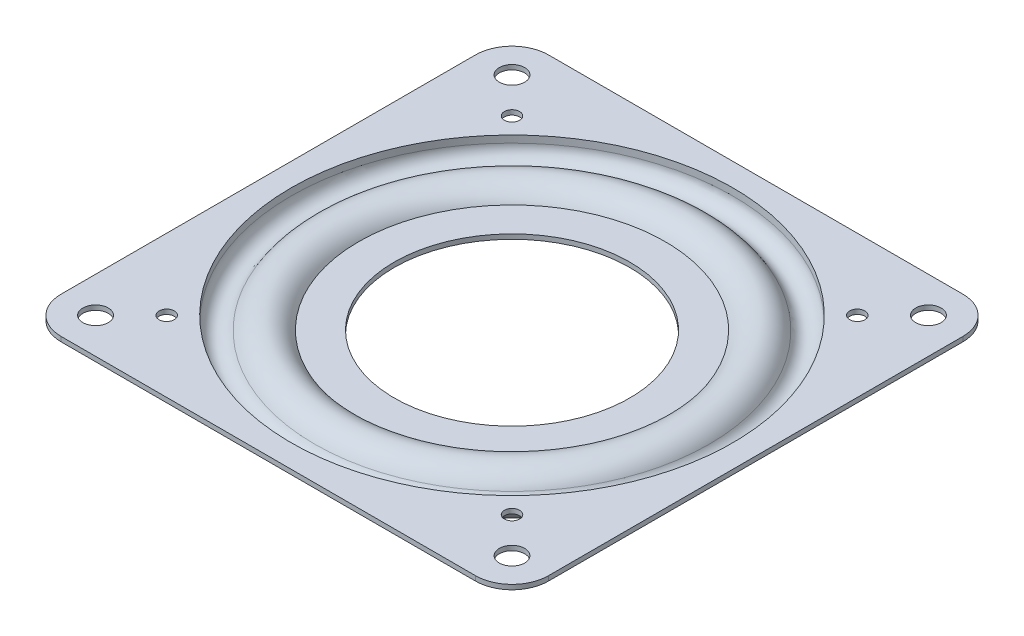
SolidWorks part; units mm, degrees
material "Plain Carbon Steel"
ref_plane "Front Plane" through (0, 0, 0) normal (0, 0, 1) x (1, 0, 0)
ref_plane "Top Plane" through (0, 0, 0) normal (0, 1, 0) x (1, 0, 0)
ref_plane "Right Plane" through (0, 0, 0) normal (1, 0, 0) x (0, 0, -1)
sketch "Sketch1" plane through (0, 0, 0) normal (0, 1, 0) x (1, 0, 0)
  line L0 (0, -53.8815) -> (-53.8815, 0) construction
  line L1 (-38.1, 38.1) -> (38.1, 38.1) construction
  line L2 (-38.1, 38.1) -> (-38.1, -38.1) construction
  line L3 (-38.1, -38.1) -> (38.1, -38.1) construction
  line L4 (38.1, 38.1) -> (38.1, -38.1) construction
  line L5 (0, -38.1) -> (0, 38.1) construction
  line L6 (-38.1, 0) -> (38.1, 0) construction
  line L7 (0, -53.8815) -> (53.8815, 0) construction
  line L8 (-53.8815, 0) -> (0, 53.8815) construction
  line L9 (53.8815, 0) -> (0, 53.8815) construction
  line L10 (0, -53.8815) -> (0, 53.8815) construction
  line L11 (-53.8815, 0) -> (53.8815, 0) construction
  line L12 (38.1, -38.1) -> (-38.1, 38.1) construction
  line L13 (38.1, 38.1) -> (-38.1, -38.1) construction
  line L15 (-26.9875, 26.9875) -> (26.9875, 26.9875) construction
  line L16 (-26.9875, 26.9875) -> (-26.9875, -26.9875) construction
  line L17 (-26.9875, -26.9875) -> (26.9875, -26.9875) construction
  line L18 (26.9875, 26.9875) -> (26.9875, -26.9875) construction
  line L19 (-32.5437, 32.5437) -> (32.5437, 32.5437) construction
  line L20 (-32.5437, 32.5437) -> (-32.5437, -32.5437) construction
  line L21 (-32.5437, -32.5437) -> (32.5437, -32.5437) construction
  line L22 (32.5437, 32.5437) -> (32.5437, -32.5437) construction
  circle A0 centre (0, 0) radius 16.637 construction
  circle A1 centre (32.5437, -32.5437) radius 1.9844 construction
  circle A2 centre (-32.5437, -32.5437) radius 1.9844 construction
  circle A3 centre (-32.5437, 32.5437) radius 1.9844 construction
  circle A4 centre (32.5437, 32.5437) radius 1.9844 construction
  circle A5 centre (26.9875, 26.9875) radius 1.1906 construction
  circle A6 centre (-26.9875, 26.9875) radius 1.1906 construction
  circle A7 centre (-26.9875, -26.9875) radius 1.1906 construction
  circle A8 centre (26.9875, -26.9875) radius 1.1906 construction
  dimension "ID" = 33.274
  dimension "Inner Mounting Hole Dia." = 2.3813
  dimension "Outer Mounting Hole Dia." = 3.9688
  dimension "Length" = 76.2
  dimension "Width" = 76.2
  dimension "Inner Mounting Length" = 53.975
  dimension "Outer Mounting Length" = 65.0875
sketch "Sketch2" plane through (0, 0, 0) normal (0, 0, 1) x (1, 0, 0)
  line L0 (0, 3.937) -> (0, -3.937) construction
  line L1 (-38.1, 3.937) -> (38.1, 3.937) construction
  line L2 (-38.1, 3.937) -> (-38.1, -3.937) construction
  line L3 (-38.1, -3.937) -> (38.1, -3.937) construction
  line L4 (38.1, 3.937) -> (38.1, -3.937) construction
  line L5 (-38.1, 0) -> (38.1, 0) construction
  line L6 (-38.1, 3.2004) -> (38.1, 3.2004) construction
  line L7 (-38.1, -3.2004) -> (38.1, -3.2004) construction
  point P8 (0, 0)
  dimension "Overall Height" = 7.874
  dimension "Plate Thickness" = 0.7366
sketch "Sketch3" plane through (0, 0, 0) normal (0, 0, 1) x (1, 0, 0)
  line L0 (38.1, 3.937) -> (34.5177, 3.937)
  line L1 (-38.1, 3.937) -> (38.1, 3.937) construction
  line L2 (34.5177, 3.937) -> (34.5177, 2.8346)
  line L3 (23.943, 1.9406) -> (18.4086, 1.9406)
  line L4 (38.1, -3.937) -> (34.5177, -3.937)
  line L5 (-38.1, -3.937) -> (38.1, -3.937) construction
  line L6 (34.5177, -3.937) -> (34.5177, -2.8346)
  line L7 (34.5177, -2.8346) -> (34.5177, 2.8346) construction
  line L8 (23.528, -0.8661) -> (18.4086, -0.8661)
  line L9 (18.4086, 2.6772) -> (20.9683, 2.6772)
  line L10 (23.528, -0.8661) -> (34.5177, -0.8661) construction
  line L11 (16.637, 3.937) -> (16.637, -3.937) construction
  line L12 (16.637, 0) -> (-16.637, 0) construction
  line L13 (18.4086, 2.6772) -> (18.4086, 1.9406) construction
  line L14 (38.1, -3.937) -> (38.1, 3.937) construction
  line L15 (27.3685, 0) -> (38.1, 0) construction
  line L16 (27.3685, 0) -> (16.637, 0) construction
  line L17 (38.1, 3.937) -> (38.1, -3.937) construction
  line L18 (20.9683, -0.8661) -> (20.9683, 2.6772) construction
  line L19 (0, 3.937) -> (0, -3.937) construction
  arc A0 (34.5177, 2.8346) -> (30.8223, 1.8898) centre (32.5492, 2.8346) cw
  circle A1 centre (27.3685, 0) radius 3.937 construction
  arc A2 (30.8223, 1.8898) -> (23.943, 1.9406) centre (27.3685, 0) ccw
  arc A3 (34.5177, -2.8346) -> (30.8223, -1.8898) centre (32.5492, -2.8346) ccw
  arc A4 (30.8223, -1.8898) -> (23.528, -0.8661) centre (27.3685, 0) cw
  arc A5 (18.4086, -0.8661) -> (18.4086, 2.6772) centre (18.4086, 0.9055) cw
  point P26 (16.637, 0)
  point P38 (19.6885, 2.6772)
  dimension "D3" = 7.874
  dimension "D4" = 1.9685
  dimension "D1" = 0.7366
  dimension "D2" = 3.5433
  dimension "D5" = 6.6142
  dimension "D6" = 3.5823
revolve "Revolve-Thin1" [suppressed] add sketch "Sketch3" angle 360 about L0 wall 0.7366
revolve "Revolve-Thin2" add sketch "Sketch3<3>" angle 360 about L0 wall 0.7366
sketch "Sketch3<3>" plane through (0, 0, 0) normal (0, 0, 1) x (1, 0, 0) same geometry as "Sketch3"
sketch "Sketch4" plane through (0, 3.937, 0) normal (0, 1, 0) x (1, 0, 0)
  line L1 (-38.1, 38.1) -> (38.1, 38.1)
  line L2 (-38.1, 38.1) -> (-38.1, -38.1)
  line L3 (-38.1, -38.1) -> (38.1, -38.1)
  line L4 (38.1, 38.1) -> (38.1, -38.1)
  circle A0 centre (0, 0) radius 34.5177 construction
  circle A1 centre (0, 0) radius 34.5177
extrude "Boss-Extrude1" add sketch "Sketch4" against normal up to vertex (0.7366 mm away) up to point (38.1, 3.2004, 0)
sketch "Sketch5" [suppressed] plane through (0, -3.937, 0) normal (0, -1, 0) x (1, 0, 0)
  line L0 (-53.8815, 0) -> (0, 53.8815)
  line L1 (0, 53.8815) -> (53.8815, 0)
  line L2 (53.8815, 0) -> (0, -53.8815)
  line L3 (0, -53.8815) -> (-53.8815, 0)
  circle A0 centre (0, 0) radius 34.5177 construction
  circle A1 centre (0, 0) radius 34.5177
extrude "Boss-Extrude2" [suppressed] add sketch "Sketch5" against normal up to vertex
sketch "Sketch6" plane through (0, 0, 0) normal (0, 1, 0) x (1, 0, 0)
  circle A0 centre (-32.5437, 32.5437) radius 1.9844 construction
  circle A1 centre (-32.5437, -32.5437) radius 1.9844 construction
  circle A2 centre (32.5437, -32.5437) radius 1.9844 construction
  circle A3 centre (32.5437, 32.5437) radius 1.9844 construction
  circle A4 centre (-32.5437, 32.5437) radius 1.9844
  circle A5 centre (-32.5437, -32.5437) radius 1.9844
  circle A6 centre (32.5437, -32.5437) radius 1.9844
  circle A7 centre (32.5437, 32.5437) radius 1.9844
  circle A8 centre (26.9875, 26.9875) radius 1.1906 construction
  circle A9 centre (-26.9875, 26.9875) radius 1.1906 construction
  circle A10 centre (26.9875, -26.9875) radius 1.1906 construction
  circle A11 centre (-26.9875, -26.9875) radius 1.1906 construction
  circle A12 centre (26.9875, 26.9875) radius 1.1906
  circle A13 centre (-26.9875, 26.9875) radius 1.1906
  circle A14 centre (26.9875, -26.9875) radius 1.1906
  circle A15 centre (-26.9875, -26.9875) radius 1.1906
extrude "Cut-Extrude1" cut sketch "Sketch6" against normal through all both and the other way through all
sketch "Sketch7" plane through (0, 0, 0) normal (0, 1, 0) x (1, 0, 0)
  line L0 (-46.0238, 0) -> (0, 46.0238) construction
  line L1 (-46.0238, 0) -> (0, -46.0238) construction
  line L2 (0, 46.0238) -> (46.0238, 0) construction
  line L3 (0, -46.0238) -> (46.0238, 0) construction
  line L4 (-46.0238, 0) -> (46.0238, 0) construction
  line L5 (0, 46.0238) -> (0, -46.0238) construction
  line L6 (-53.8815, 0) -> (53.8815, 0) construction
  line L7 (0, -53.8815) -> (0, 53.8815) construction
  line L8 (-32.5437, -32.5437) -> (32.5437, -32.5437) construction
  circle A0 centre (46.0238, 0) radius 1.9844
  circle A1 centre (0, 46.0238) radius 1.9844
  circle A2 centre (-46.0238, 0) radius 1.9844
  circle A3 centre (0, -46.0238) radius 1.9844
  circle A4 centre (32.5437, -32.5437) radius 1.9844 construction
  circle A5 centre (32.5437, -32.5437) radius 1.9844 construction
  point P1 (0, 0)
extrude "Cut-Extrude2" [suppressed] cut sketch "Sketch7" against normal through all both and the other way through all
sketch "Sketch8" plane through (0, 0, 0) normal (0, 0, 1) x (1, 0, 0)
  line L0 (27.3685, 3.683) -> (27.3685, -3.683)
  arc A1 (27.3685, 3.683) -> (27.3685, -3.683) centre (27.3685, 0) cw
  circle A2 centre (27.3685, 0) radius 3.683
  circle A3 centre (27.3685, 0) radius 3.683 construction
  dimension "D1" = 0.254
revolve "Revolve1" add sketch "Sketch8" angle 360 about L0
pattern_circular "CirPattern1" count 22 over 360 about axis through (0, 3.937, 0) along (0, -1, 0) of bodies 110
fillet "Fillet1" radius 5.715 4 edges at (-38.1, 3.5687, -38.1) (38.1, 3.5687, -38.1) (-38.1, 3.5687, 38.1) (38.1, 3.5687, 38.1)
fillet "Fillet2" [suppressed] radius 5.715
equation "\"D1@Sketch3\"=\"Plate Thickness@Sketch2\""
equation "\"D2@Sketch3\"=\"Overall Height@Sketch2\"*.45"
equation "\"D5@Sketch3\"=\"Overall Height@Sketch2\"*.84"
equation "\"D4@Sketch3\"=\"D3@Sketch3\"*.25"
equation "\"D3@Revolve-Thin2\"=\"Plate Thickness@Sketch2\""
equation "\"D3@Revolve-Thin1\"=\"Plate Thickness@Sketch2\""
equation "\"D1@Fillet2\"=\"D1@Fillet1\""
equation "\"D1@Fillet1\"=\"Length@Sketch1\"*.075"
